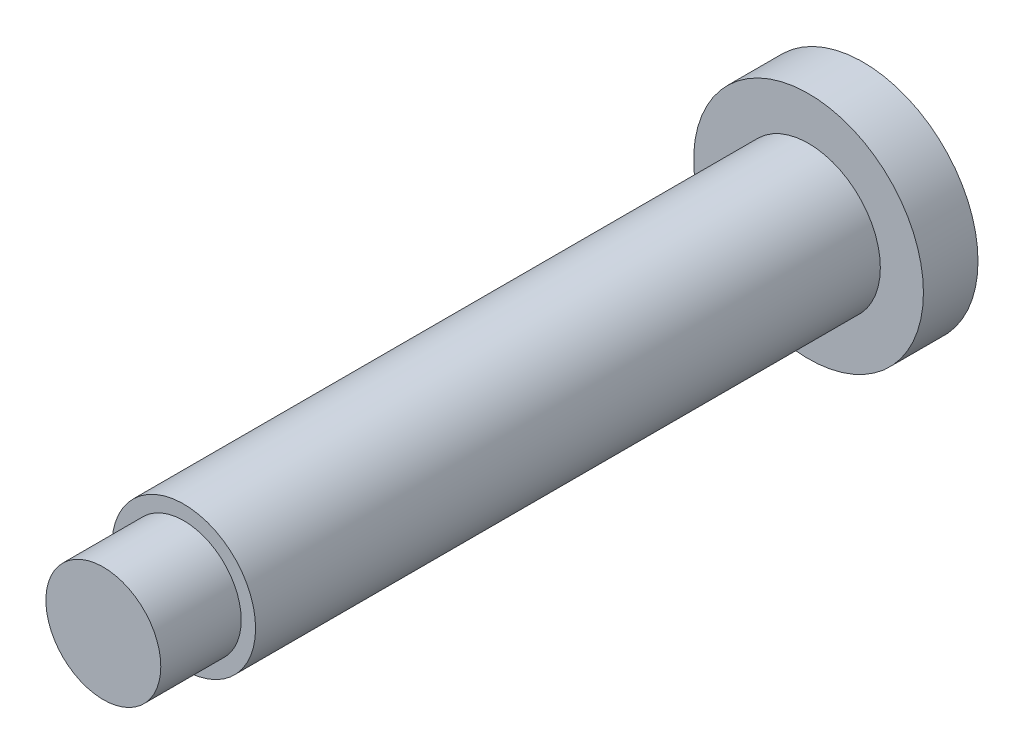
SolidWorks part; units mm, degrees
ref_plane "Front Plane" through (0, 0, 0) normal (1, 0, 0) x (0, 1, 0)
ref_plane "Top Plane" through (0, 0, 0) normal (0, 0, 1) x (0, 1, 0)
ref_plane "Right Plane" through (0, 0, 0) normal (0, 1, 0) x (-1, 0, 0)
sketch "Sketch1" plane through (0, 0, 0) normal (0, 0, 1) x (0, 1, 0)
  circle A0 centre (0, 0) radius 2.5
extrude "Boss-Extrude1" add sketch "Sketch1" along normal blind 21.75 contours A0
sketch "Sketch2" plane through (0, 0, 0) normal (0, 0, -1) x (1, 0, 0)
  circle A0 centre (0, 0) radius 4
extrude "Boss-Extrude2" add sketch "Sketch2" along normal blind 1.9
sketch "Sketch3" plane through (0, 0, -1.9) normal (0, 0, -1) x (1, 0, 0)
  circle A0 centre (0, 0) radius 2.05
extrude "Cut-Extrude1" cut sketch "Sketch3" against normal blind 3
sketch "Sketch4" plane through (0, 0, 21.75) normal (0, 0, 1) x (1, 0, 0)
  circle A0 centre (0, 0) radius 2
extrude "Boss-Extrude3" add sketch "Sketch4" along normal blind 2.8
